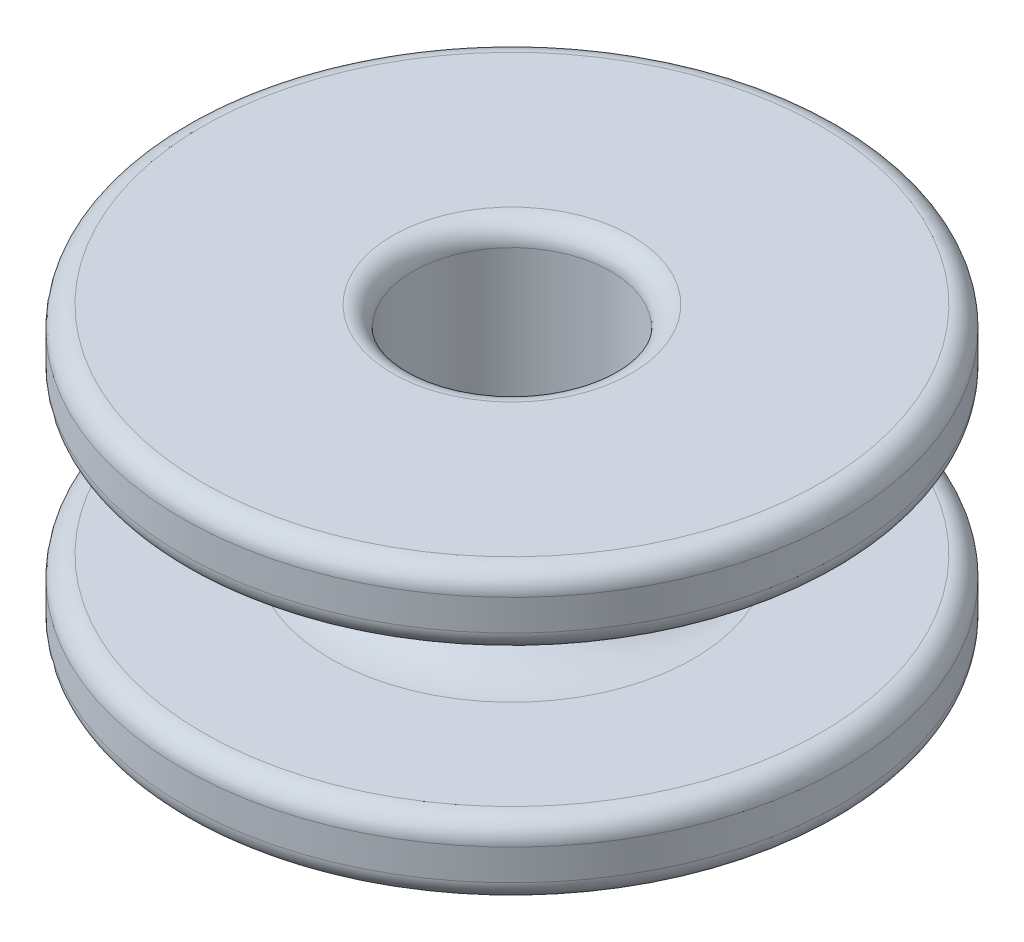
SolidWorks part; units mm, degrees
ref_plane "Front Plane" through (0, 0, 0) normal (0, 0, 1) x (1, 0, 0)
ref_plane "Top Plane" through (0, 0, 0) normal (0, 1, 0) x (1, 0, 0)
ref_plane "Right Plane" through (0, 0, 0) normal (1, 0, 0) x (0, 0, -1)
sketch "Sketch1" plane through (0, 0, 0) normal (0, 0, 1) x (1, 0, 0)
  line L0 (-1.2, 0) -> (6.8, 0) construction
  line L1 (-1.2, -3.5) -> (1.2, -3.5) construction
  line L2 (-1.2, -3.5) -> (-1.2, 3.5) construction
  line L3 (-1.2, 3.5) -> (1.2, 3.5) construction
  line L4 (1.2, -3.5) -> (1.2, 3.5)
  line L5 (-1.2, -3.5) -> (1.2, 3.5) construction
  line L6 (-1.2, 3.5) -> (1.2, -3.5) construction
  line L7 (6.8, 3.5) -> (6.8, -3.5) construction
  line L8 (1.2, 3.5) -> (6.8, 3.5)
  line L9 (1.2, 3.5) -> (1.2, -3.5)
  line L10 (1.2, -3.5) -> (6.8, -3.5)
  line L11 (6.8, 3.5) -> (6.8, 1.75)
  line L12 (6.8, -1.75) -> (6.8, -3.5)
  line L13 (1.2, 1.1727) -> (3.2, 1.1727) construction
  line L16 (3.2, 0) -> (6.8, 0) construction
  line L17 (3.2, 1.75) -> (6.8, 1.75)
  line L18 (3.2, -1.75) -> (6.8, -1.75)
  arc A5 (3.2, 1.75) -> (3.2, -1.75) centre (3.2, 0) ccw
  arc A6 (6.8, -1.75) -> (6.8, 1.75) centre (6.8, 0) ccw
  point P0 (0, 0)
  point P15 (5, 0)
  point P18 (3.2, 0)
  point P21 (0, 0)
  dimension "D4" = 5.6
  dimension "D1" = 2.4
  dimension "D2" = 7
  dimension "D3" = 8
revolve "Revolve1" add sketch "Sketch1" angle 360 about L2 region at (1.2896, 0, 0)
fillet "Fillet1" radius 0.5 6 edges at (-1.2, -3.5, -2.4) (-1.2, -3.5, -8) (-1.2, 3.5, -2.4) (-1.2, 3.5, -8) (-1.2, -1.75, -8) (-1.2, 1.75, -8)
